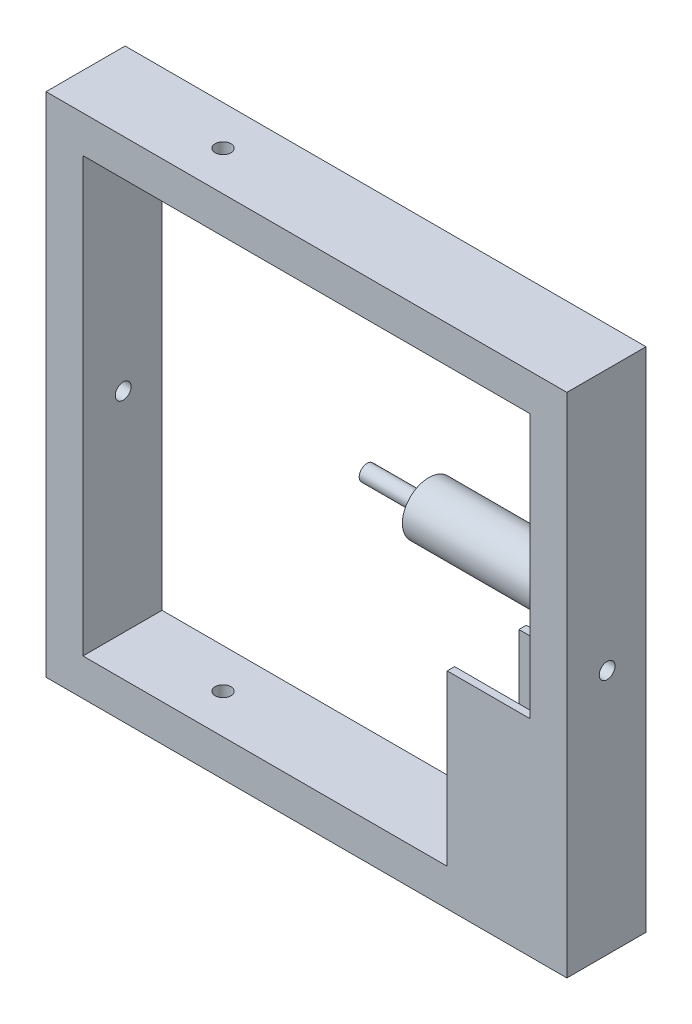
SolidWorks part; units mm, degrees
ref_plane "Front" through (0, 0, 0) normal (0, 0, 1) x (1, 0, 0)
ref_plane "Top" through (0, 0, 0) normal (0, 1, 0) x (1, 0, 0)
ref_plane "Right" through (0, 0, 0) normal (1, 0, 0) x (0, 0, -1)
sketch "Эскиз1" plane through (0, 0, 0) normal (0, 0, 1) x (1, 0, 0)
  line L5 (0, 0) -> (98.8, 0)
  line L6 (0, 0) -> (0, -96.2)
  line L7 (0, -96.2) -> (98.8, -96.2)
  line L8 (98.8, 0) -> (98.8, -96.2)
  dimension "D1" = 98.8
  dimension "D2" = 96.2
extrude "Бобышка-Вытянуть2" add sketch "Эскиз1" along normal blind 15
sketch "Эскиз4" plane through (0, 0, 15) normal (0, 0, 1) x (1, 0, 0)
  line L0 (98.8, 0) -> (0, 0) construction
  line L1 (7, -7) -> (91.8, -7)
  line L2 (7, -7) -> (7, -89.2)
  line L3 (7, -89.2) -> (91.8, -89.2)
  line L4 (91.8, -7) -> (91.8, -89.2)
  line L5 (98.8, -96.2) -> (98.8, 0) construction
  point P4 (49.4, -7)
  point P5 (49.4, 0)
  point P9 (91.8, -48.1)
  point P11 (98.8, -48.1)
  dimension "D1" = 84.8
  dimension "D2" = 82.2
extrude "Вырез-Вытянуть1" cut sketch "Эскиз4" against normal blind 57 and the other way blind 43
sketch "Эскиз9" plane through (0, 0, 0) normal (1, 0, 0) x (0, 0, -1)
  line L13 (-12.7647, -25.339) -> (-5.1387, -25.339)
  line L14 (-12.7647, -25.339) -> (-12.7647, -40.3629)
  line L15 (-12.7647, -40.3629) -> (-5.1387, -40.3629)
  line L16 (-5.1387, -25.339) -> (-5.1387, -40.3629)
sketch "Эскиз10" plane through (98.8, 0, 0) normal (1, 0, 0) x (0, 0, -1)
  line L0 (0, -96.2) -> (0, 0) construction
  line L5 (0, -57.1) -> (-15, -57.1)
  line L6 (0, -57.1) -> (0, -89.2)
  line L7 (0, -89.2) -> (-15, -89.2)
  line L8 (-15, -57.1) -> (-15, -89.2)
  line L9 (-15, -96.2) -> (0, -96.2) construction
  dimension "D1" = 15
  dimension "D2" = 32.1
  dimension "D3" = 0
  dimension "D4" = 7
extrude "Бобышка-Вытянуть4" add sketch "Эскиз10" against normal blind 16
sketch "Эскиз11" plane through (82.8, 0, 0) normal (-1, 0, 0) x (0, 0, 1)
  line L0 (0, -89.2) -> (0, -57.1) construction
  line L1 (1.4, -57) -> (13.6, -57)
  line L2 (1.4, -57) -> (1.4, -85.2)
  line L3 (1.4, -85.2) -> (13.6, -85.2)
  line L4 (13.6, -57) -> (13.6, -85.2)
  line L5 (15, -89.2) -> (0, -89.2) construction
  dimension "D1" = 12.2
  dimension "D2" = 28.2
  dimension "D3" = 1.4
  dimension "D4" = 4
extrude "Вырез-Вытянуть2" cut sketch "Эскиз11" against normal blind 9
sketch "Эскиз12" plane through (91.8, 0, 0) normal (-1, 0, 0) x (0, 0, 1)
  line L0 (15, -7) -> (15, -57.1) construction
  line L1 (1.4, -85.2) -> (13.6, -85.2) construction
  circle A1 centre (7.5, -39.6) radius 5.0115
  dimension "D1" = 7.5
  dimension "D2" = 45.6
extrude "Бобышка-Вытянуть5" add sketch "Эскиз12" along normal blind 26.7
sketch "Эскиз13" plane through (65.1, 0, 0) normal (-1, 0, 0) x (0, 0, 1)
  circle A0 centre (7.5, -39.6) radius 1.5
extrude "Бобышка-Вытянуть6" add sketch "Эскиз13" along normal blind 11.7
sketch "Эскиз14" plane through (82.8, 0, 0) normal (-1, 0, 0) x (0, 0, 1)
  line L0 (0, -89.2) -> (0, -57.1) construction
  line L1 (0, -85.2152) -> (15, -85.2152)
  line L2 (0, -85.2152) -> (0, -89.2)
  line L3 (0, -89.2) -> (15, -89.2)
  line L4 (15, -85.2152) -> (15, -89.2)
  dimension "D1" = 15
extrude "Бобышка-Вытянуть7" add sketch "Эскиз14" along normal blind 6.7
fillet "Скругление1" radius 10 1 edges at (82.8, -85.2, 7.5)
sketch "Эскиз15" plane through (82.8, 0, 0) normal (-1, 0, 0) x (0, 0, 1)
  line L1 (0, -57.1) -> (1.4, -57.1)
  line L2 (0, -57.1) -> (0, -85.2152)
  line L3 (0, -85.2152) -> (1.4, -85.2152)
  line L4 (1.4, -57.1) -> (1.4, -85.2152)
extrude "Бобышка-Вытянуть8" add sketch "Эскиз15" along normal blind 6.7
sketch "Эскиз17" plane through (82.8, 0, 0) normal (-1, 0, 0) x (0, 0, 1)
  line L1 (13.6, -57.1) -> (15, -57.1)
  line L2 (13.6, -57.1) -> (13.6, -85.2152)
  line L3 (13.6, -85.2152) -> (15, -85.2152)
  line L4 (15, -57.1) -> (15, -85.2152)
extrude "Бобышка-Вытянуть9" add sketch "Эскиз17" along normal blind 6.7
sketch "Эскиз18" plane through (7, 0, 0) normal (1, 0, 0) x (0, 0, -1)
  circle A0 centre (-7.3656, -49.5018) radius 1.5
  point P2 (0, 0)
extrude "Вырез-Вытянуть3" cut sketch "Эскиз18" against normal blind 32.7 and the other way blind 128
sketch "Эскиз19" plane through (0, -89.2, 0) normal (0, 1, 0) x (1, 0, 0)
  line L0 (76.1, 0) -> (7, 0) construction
  circle A0 centre (26.0809, -7.5) radius 1.5
  dimension "D1" = 7.5
extrude "Вырез-Вытянуть4" cut sketch "Эскиз19" against normal blind 39.7 and the other way blind 107
